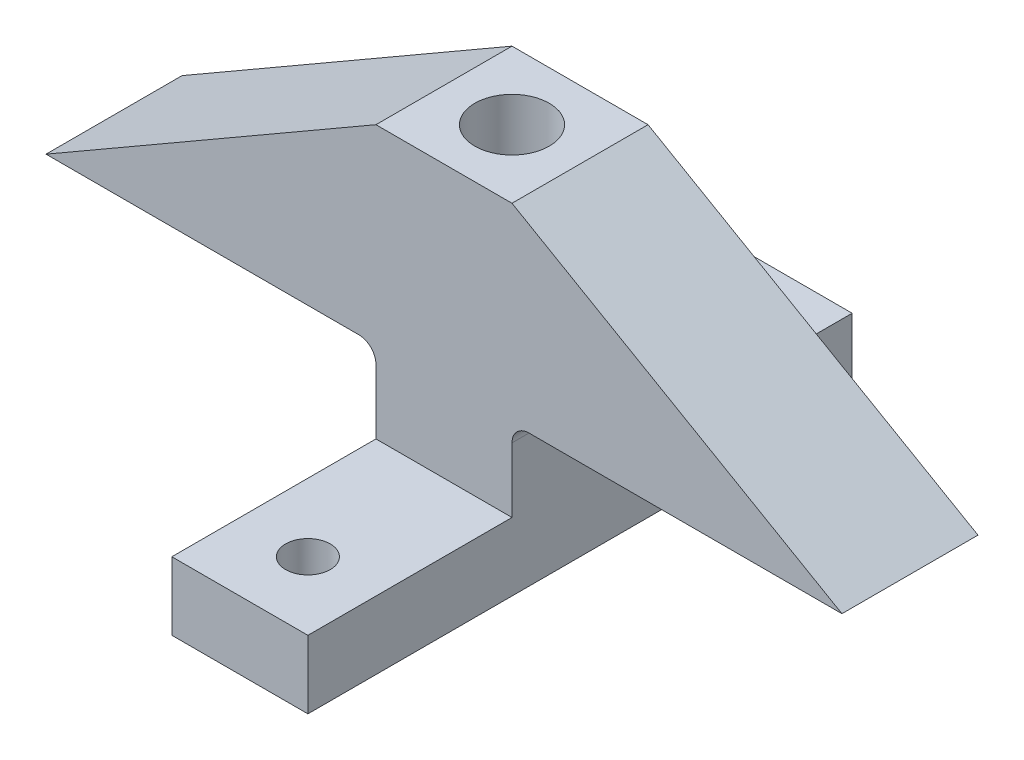
SolidWorks part; units mm, degrees
material "PET"
ref_plane "Front Plane" through (0, 0, 0) normal (0, 0, 1) x (1, 0, 0)
ref_plane "Top Plane" through (0, 0, 0) normal (0, 1, 0) x (1, 0, 0)
ref_plane "Right Plane" through (0, 0, 0) normal (1, 0, 0) x (0, 0, -1)
sketch "Sketch1" plane through (0, 0, 0) normal (0, 0, 1) x (1, 0, 0)
  line L0 (0, 0) -> (0, 27.94)
  line L1 (0, 27.94) -> (-61.5917, 27.94)
  line L2 (-61.5917, 27.94) -> (0, 63.5)
  line L3 (0, 63.5) -> (25.4, 63.5)
  line L4 (25.4, 63.5) -> (86.9917, 27.94)
  line L5 (86.9917, 27.94) -> (25.4, 27.94)
  line L6 (25.4, 27.94) -> (25.4, 0)
  line L7 (25.4, 0) -> (0, 0)
  point P9 (12.7, 63.5)
  point P10 (12.7, 0)
  dimension "D1" = 35.56
  dimension "D2" = 25.4
  dimension "D3" = 30
  dimension "D4" = 30
  dimension "D5" = 25.4
  dimension "D6" = 63.5
extrude "Boss-Extrude1" add sketch "Sketch1" along normal blind 25.4
sketch "Sketch2" plane through (0, 0, 25.4) normal (0, 0, 1) x (1, 0, 0)
  line L1 (0, 0) -> (25.4, 0)
  line L2 (0, 0) -> (0, 12.7)
  line L3 (0, 12.7) -> (25.4, 12.7)
  line L4 (25.4, 0) -> (25.4, 12.7)
  line L5 (25.4, 0) -> (25.4, 27.94) construction
  point P5 (0, 0)
  dimension "D1" = 12.7
extrude "Boss-Extrude2" add sketch "Sketch2" along normal blind 38.1
sketch "Sketch3" plane through (0, 0, 0) normal (0, 0, -1) x (-1, 0, 0)
  line L0 (0, 27.94) -> (0, 0) construction
  line L1 (-25.4, 0) -> (0, 0)
  line L2 (-25.4, 0) -> (-25.4, 13.97)
  line L3 (-25.4, 13.97) -> (0, 13.97)
  line L4 (0, 0) -> (0, 13.97)
extrude "Boss-Extrude3" add sketch "Sketch3" along normal blind 38.1
hole_wizard "Ø0.328in Dowel Hole1" positions "Sketch4" profile "Sketch5" hole size "Ø1.0" standard "ISO" end condition through all
sketch "Sketch4" plane through (0, 13.97, 0) normal (0, 1, 0) x (1, 0, 0)
  point P0 (12.7, 25.4)
  point P2 (12.7, -50.8)
  point P12 (0, 0)
  dimension "D1" = 12.7
  dimension "D2" = 12.7
  dimension "D3" = 12.7
  dimension "D4" = 12.7
sketch "Sketch5" plane through (12.7, 13.97, -25.4) normal (1, 0, 0) x (0, 0, 1)
  line L0 (0, 0) -> (0, 13.97)
  line L1 (0, 13.97) -> (4.1656, 13.97)
  line L2 (4.1656, 13.97) -> (4.1656, 0)
  line L5 (4.1656, 0) -> (0, 0)
  line L11 (0, -6.35) -> (0, 107.95) construction
  dimension "Thru Hole Dia." = 8.3312
  dimension "Thru Hole Depth" = 13.97
hole_wizard "Ø0.55in Dowel Hole2" positions "Sketch7" profile "Sketch6" hole size "Ø1.0" standard "ISO"
sketch "Sketch7" plane through (0, 63.5, 0) normal (0, 1, 0) x (1, 0, 0)
  point P0 (12.7, -12.7)
  dimension "D1" = 12.7
  dimension "D2" = 12.7
sketch "Sketch6" plane through (12.7, 63.5, 12.7) normal (1, 0, 0) x (0, 0, 1)
  line L0 (0, 0) -> (0, 39.2261)
  line L1 (0, 39.2261) -> (6.9469, 35.052)
  line L2 (6.9469, 35.052) -> (6.9469, 0)
  line L5 (6.9469, 0) -> (0, 0)
  line L10 (0, 39.2261) -> (-6.9469, 35.052) construction
  line L11 (0, -6.35) -> (0, 107.95) construction
  dimension "Hole Dia." = 13.8938
  dimension "Hole Depth" = 35.052
  dimension "Drill Angle" = 118
fillet "Fillet1" radius 3.175 2 edges at (25.4, 27.94, 12.7) (0, 27.94, 12.7)
